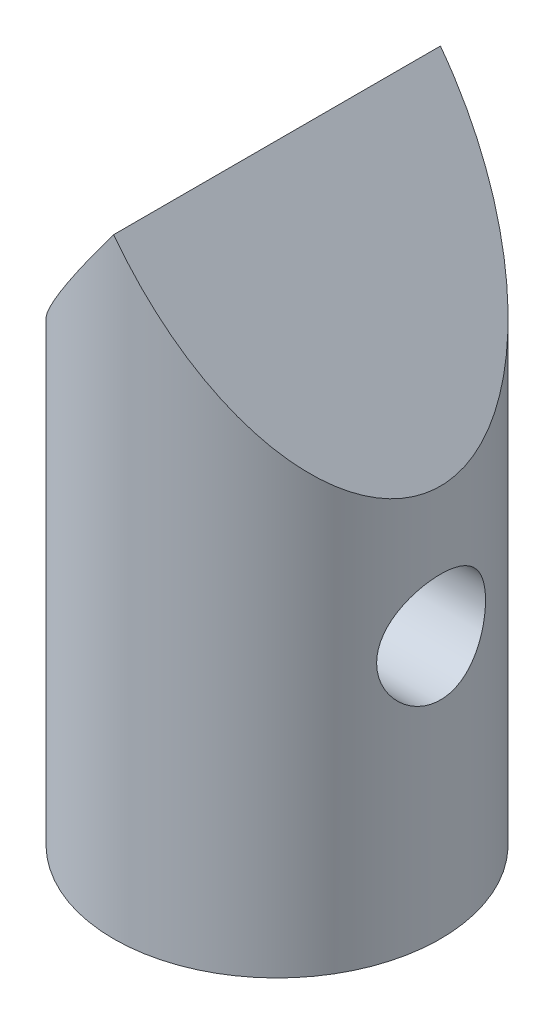
SolidWorks part; units mm, degrees
ref_plane "Front Plane" through (0, 0, 0) normal (0, 0, 1) x (1, 0, 0)
ref_plane "Top Plane" through (0, 0, 0) normal (0, 1, 0) x (1, 0, 0)
ref_plane "Right Plane" through (0, 0, 0) normal (1, 0, 0) x (0, 0, -1)
sketch "Sketch1" plane through (0, 0, 0) normal (0, 1, 0) x (1, 0, 0)
  circle A0 centre (0, 0) radius 4.7625
  dimension "D1" = 9.525
extrude "Boss-Extrude1" add sketch "Sketch1" along normal blind 17.78
sketch "Sketch2" plane through (0, 0, 0) normal (0, 0, 1) x (1, 0, 0)
  line L0 (-4.7625, 17.78) -> (0, 17.78)
  line L3 (4.7625, 17.78) -> (-4.7625, 17.78) construction
  line L5 (-4.7625, 17.78) -> (-4.7625, 11.43)
  line L6 (-4.7625, 17.78) -> (-4.7625, 0) construction
  line L7 (0, 17.78) -> (-4.7625, 11.43)
  dimension "D2" = 6.35
extrude "Cut-Extrude1" cut sketch "Sketch2" against normal blind 17.78 and the other way blind 17.78
sketch "Sketch3" plane through (0, 0, 0) normal (0, 0, 1) x (1, 0, 0)
  line L0 (0, 17.78) -> (4.7625, 17.78)
  line L1 (4.7625, 17.78) -> (4.7625, 11.43)
  line L2 (4.7625, 0) -> (4.7625, 17.78) construction
  line L3 (4.7625, 11.43) -> (0, 17.78)
  dimension "D1" = 6.35
extrude "Cut-Extrude2" cut sketch "Sketch3" against normal blind 17.78 and the other way blind 17.78
sketch "Sketch4" plane through (0, 0, 0) normal (1, 0, 0) x (0, 0, -1)
  line L0 (-4.7625, 0) -> (4.7625, 0) construction
  circle A0 centre (0, 7.62) radius 1.5875
  dimension "D2" = 3.175
  dimension "D1" = 7.62
extrude "Cut-Extrude3" cut sketch "Sketch4" against normal blind 17.78 and the other way blind 17.78
